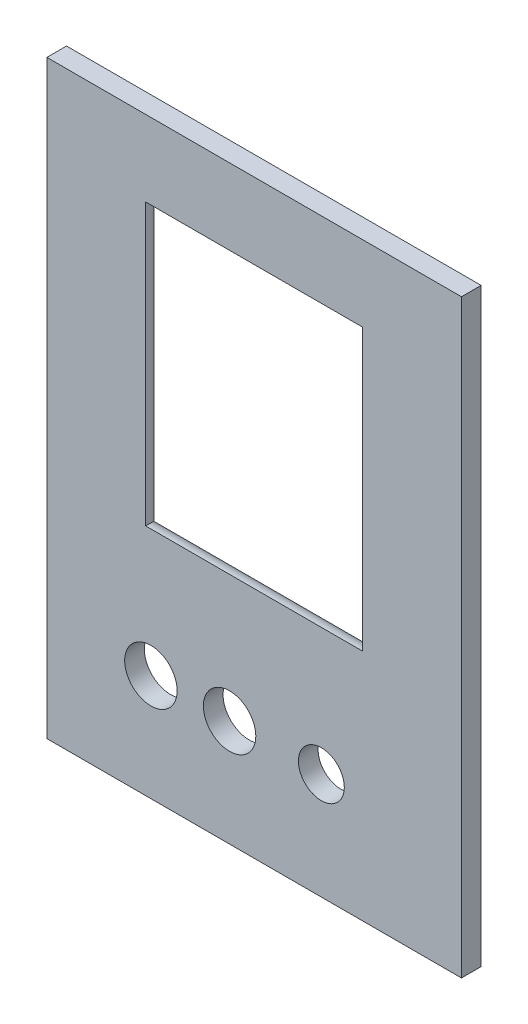
SolidWorks part; units mm, degrees
ref_plane "Спереди" through (0, 0, 0) normal (0, 0, 1) x (1, 0, 0)
ref_plane "Сверху" through (0, 0, 0) normal (0, 1, 0) x (1, 0, 0)
ref_plane "Справа" through (0, 0, 0) normal (1, 0, 0) x (0, 0, -1)
ref_plane "Плоскость1" through (0, -42.8486, -15.5956) normal (0, -0.9397, -0.342) x (-1, 0, 0)
sketch "Эскиз1" plane through (0, 0, 0) normal (0, 0, 1) x (1, 0, 0)
  line L1 (31.625, -48.0063) -> (-31.625, -48.0063)
  line L2 (31.625, -48.0063) -> (31.625, 41.9937)
  line L3 (31.625, 41.9937) -> (-31.625, 41.9937)
  line L4 (-31.625, -48.0063) -> (-31.625, 41.9937)
  line L5 (31.625, -48.0063) -> (-31.625, 41.9937) construction
  line L6 (31.625, 41.9937) -> (-31.625, -48.0063) construction
  line L8 (-31.625, 46.6633) -> (-31.625, -65.1601) construction
  point P0 (0, -3.0063)
  dimension "D1" = 90
extrude "Бобышка-Вытянуть1" add sketch "Эскиз1" along normal blind 3
sketch "Эскиз2" plane through (0, 0, 0) normal (0, 0, 1) x (1, 0, 0)
  line L16 (16.55, -12.3685) -> (16.55, 30.4315)
  line L17 (-16.55, -12.3685) -> (16.55, -12.3685)
  line L18 (-16.55, 30.4315) -> (-16.55, -12.3685)
  line L19 (16.55, 30.4315) -> (-16.55, 30.4315)
  line L20 (16.55, -12.3685) -> (16.55, 30.4315)
  line L21 (-16.55, -12.3685) -> (16.55, -12.3685)
  line L22 (-16.55, 30.4315) -> (-16.55, -12.3685)
  line L23 (16.55, 30.4315) -> (-16.55, 30.4315)
  circle A2 centre (10.25, -31.7685) radius 3.5
  circle A3 centre (10.25, -31.7685) radius 3.5
  circle A4 centre (-3.75, -31.7535) radius 4
  circle A5 centre (-15.75, -31.7535) radius 4
  dimension "D3" = 8
  dimension "D1" = 0
  dimension "D2" = 0.5
extrude "Вырез-Вытянуть1" cut sketch "Эскиз2" along normal through all
fillet "Скругление1" radius 3 4 edges at (0, -12.3685, 0) (16.55, 9.0315, 0) (0, 30.4315, 0) (-16.55, 9.0315, 0)
